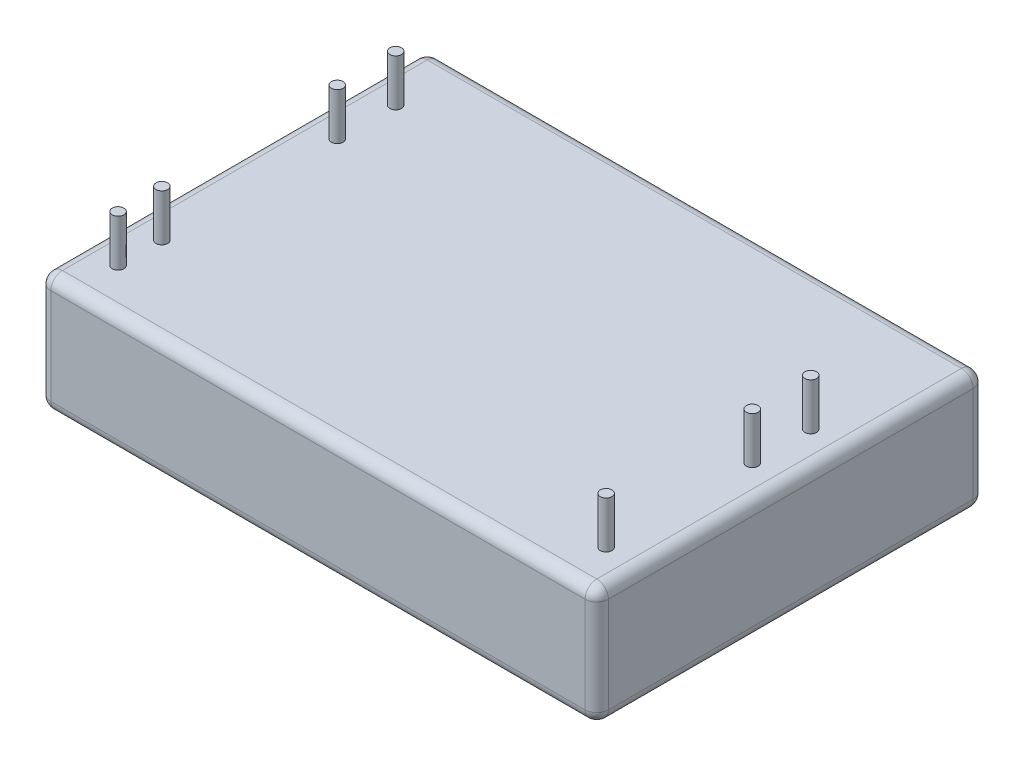
SolidWorks part; units mm, degrees
ref_plane "Спереди" through (0, 0, 0) normal (0, 0, 1) x (1, 0, 0)
ref_plane "Сверху" through (0, 0, 0) normal (0, 1, 0) x (1, 0, 0)
ref_plane "Справа" through (0, 0, 0) normal (1, 0, 0) x (0, 0, -1)
sketch "Эскиз1" plane through (0, 0, 0) normal (0, 1, 0) x (1, 0, 0)
  line L1 (-23.85, 16.6) -> (23.85, 16.6)
  line L2 (-23.85, 16.6) -> (-23.85, -16.6)
  line L3 (-23.85, -16.6) -> (23.85, -16.6)
  line L4 (23.85, 16.6) -> (23.85, -16.6)
  line L5 (-23.85, 16.6) -> (23.85, -16.6) construction
  line L6 (-23.85, -16.6) -> (23.85, 16.6) construction
  point P0 (0, 0)
  dimension "D1" = 47.7
  dimension "D2" = 33.2
extrude "Бобышка-Вытянуть1" add sketch "Эскиз1" along normal blind 10.2
sketch "Эскиз2" plane through (0, 10.2, 0) normal (0, 1, 0) x (1, 0, 0)
  line L0 (-20.85, -12.85) -> (-20.35, -12.85) construction
  line L1 (-23.85, 19.0459) -> (-20.85, 19.0459) construction
  line L2 (-20.85, 19.0459) -> (-20.85, 16.6) construction
  line L3 (23.85, 16.6) -> (-23.85, 16.6) construction
  circle A0 centre (-20.85, 5.9) radius 0.5
  circle A1 centre (-20.85, 10.9) radius 0.5
  circle A2 centre (-20.85, -12.85) radius 0.5
  circle A3 centre (-20.85, -9.1) radius 0.5
  circle A4 centre (20.9, -12.85) radius 0.5
  circle A5 centre (20.9, -0.35) radius 0.5
  circle A6 centre (20.9, 4.65) radius 0.5
extrude "Бобышка-Вытянуть2" add sketch "Эскиз2" along normal blind 4
fillet "Скругление1" radius 1 2 edges at (-23.85, 0, 0) (0, 0, 16.6)
fillet "Скругление2" radius 1 6 edges at (23.85, 5.6, 16.6) (23.85, 0.2929, 16.3071) (-23.85, 5.6, -16.6) (-23.5571, 0.2929, -16.6) (23.85, 0, -0.5) (0.5, 0, -16.6)
fillet "Скругление3" radius 1 8 edges at (0.5, 10.2, -16.6) (-23.5571, 10.2, -16.3071) (-23.5571, 0.2929, 16.3071) (23.85, 10.2, -0.5) (23.5571, 10.2, 16.3071) (-23.85, 10.2, 0.5) (-23.85, 5.6, 16.6) (-0.5, 10.2, 16.6)
fillet "Скругление4" radius 1 3 edges at (23.5571, 9.9071, -16.3071) (23.5571, 0.2929, -16.3071) (23.85, 5.1, -16.6)
